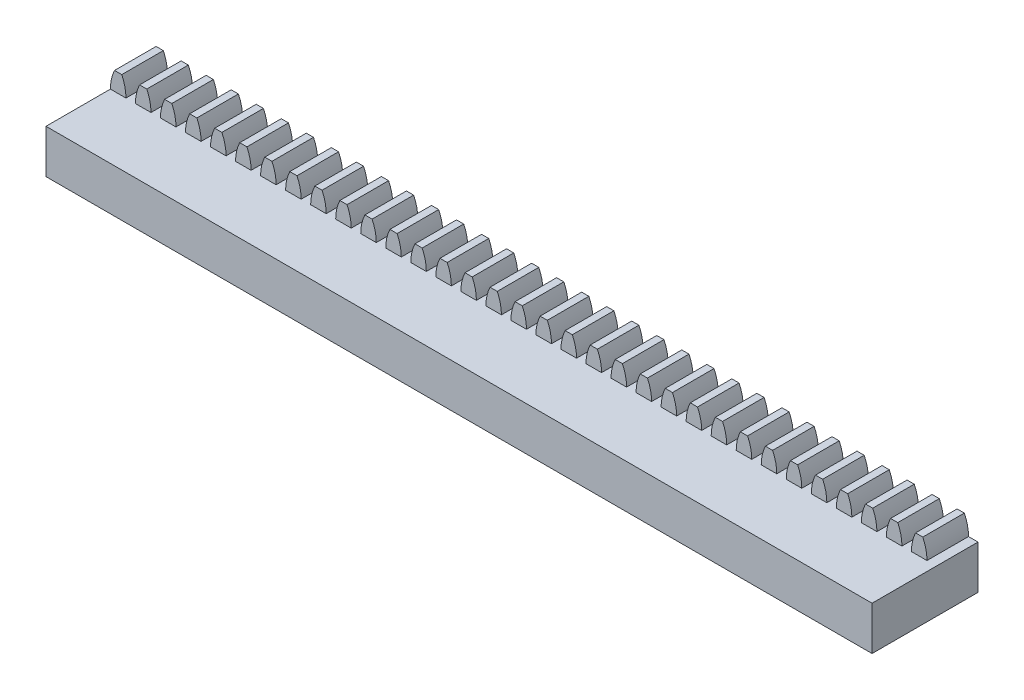
SolidWorks part; units mm, degrees
material "ABS"
ref_plane "Plano frontal" through (0, 0, 0) normal (0, 0, 1) x (1, 0, 0)
ref_plane "Plano superior" through (0, 0, 0) normal (0, 1, 0) x (1, 0, 0)
ref_plane "Plano direito" through (0, 0, 0) normal (1, 0, 0) x (0, 0, -1)
sketch "Esboço1" plane through (0, 0, 0) normal (0, 0, 1) x (1, 0, 0)
  line L0 (-1.7112, 4.5297) -> (-1.0175, 4.5297)
  line L1 (0.6988, 4.5297) -> (1.3925, 4.5297)
  line L2 (0.2978, 2.7713) -> (2.7078, 2.7713)
  line L3 (-2.1122, 2.7713) -> (0.2978, 2.7713)
  line L4 (3.1088, 4.5297) -> (3.8025, 4.5297)
  line L5 (2.7078, 2.7713) -> (5.1178, 2.7713)
  line L6 (5.5188, 4.5297) -> (6.2125, 4.5297)
  line L7 (5.1178, 2.7713) -> (7.5278, 2.7713)
  line L8 (7.9288, 4.5297) -> (8.6225, 4.5297)
  line L9 (7.5278, 2.7713) -> (9.9378, 2.7713)
  line L10 (10.3388, 4.5297) -> (11.0325, 4.5297)
  line L11 (9.9378, 2.7713) -> (12.3478, 2.7713)
  line L12 (12.7488, 4.5297) -> (13.4425, 4.5297)
  line L13 (12.3478, 2.7713) -> (14.7578, 2.7713)
  line L14 (15.1588, 4.5297) -> (15.8525, 4.5297)
  line L15 (14.7578, 2.7713) -> (17.1678, 2.7713)
  line L16 (17.5688, 4.5297) -> (18.2625, 4.5297)
  line L17 (17.1678, 2.7713) -> (19.5778, 2.7713)
  line L18 (19.9788, 4.5297) -> (20.6725, 4.5297)
  line L19 (19.5778, 2.7713) -> (21.9878, 2.7713)
  line L20 (22.3888, 4.5297) -> (23.0825, 4.5297)
  line L21 (21.9878, 2.7713) -> (24.3978, 2.7713)
  line L22 (24.7988, 4.5297) -> (25.4925, 4.5297)
  line L23 (24.3978, 2.7713) -> (26.8078, 2.7713)
  line L24 (27.2088, 4.5297) -> (27.9025, 4.5297)
  line L25 (26.8078, 2.7713) -> (29.2178, 2.7713)
  line L26 (29.6188, 4.5297) -> (30.3125, 4.5297)
  line L27 (29.2178, 2.7713) -> (31.6278, 2.7713)
  line L28 (32.0288, 4.5297) -> (32.7225, 4.5297)
  line L29 (31.6278, 2.7713) -> (34.0378, 2.7713)
  line L30 (34.4388, 4.5297) -> (35.1325, 4.5297)
  line L31 (34.0378, 2.7713) -> (36.4478, 2.7713)
  line L32 (36.8488, 4.5297) -> (37.5425, 4.5297)
  line L33 (36.4478, 2.7713) -> (38.8578, 2.7713)
  line L34 (39.2588, 4.5297) -> (39.9525, 4.5297)
  line L35 (38.8578, 2.7713) -> (41.2678, 2.7713)
  line L36 (41.6688, 4.5297) -> (42.3625, 4.5297)
  line L37 (41.2678, 2.7713) -> (43.6778, 2.7713)
  line L38 (44.0788, 4.5297) -> (44.7725, 4.5297)
  line L39 (43.6778, 2.7713) -> (46.0878, 2.7713)
  line L40 (46.4888, 4.5297) -> (47.1825, 4.5297)
  line L41 (46.0878, 2.7713) -> (48.4978, 2.7713)
  line L42 (77.4178, 2.7713) -> (77.4178, -1.4287)
  line L43 (48.8988, 4.5297) -> (49.5925, 4.5297)
  line L44 (48.4978, 2.7713) -> (50.9078, 2.7713)
  line L45 (51.3088, 4.5297) -> (52.0025, 4.5297)
  line L46 (50.9078, 2.7713) -> (53.3178, 2.7713)
  line L47 (53.7188, 4.5297) -> (54.4125, 4.5297)
  line L48 (53.3178, 2.7713) -> (55.7278, 2.7713)
  line L49 (56.1288, 4.5297) -> (56.8225, 4.5297)
  line L50 (55.7278, 2.7713) -> (58.1378, 2.7713)
  line L51 (58.5388, 4.5297) -> (59.2325, 4.5297)
  line L52 (58.1378, 2.7713) -> (60.5478, 2.7713)
  line L53 (60.9488, 4.5297) -> (61.6425, 4.5297)
  line L54 (60.5478, 2.7713) -> (62.9578, 2.7713)
  line L55 (63.3588, 4.5297) -> (64.0525, 4.5297)
  line L56 (62.9578, 2.7713) -> (65.3678, 2.7713)
  line L57 (65.7688, 4.5297) -> (66.4625, 4.5297)
  line L58 (65.3678, 2.7713) -> (67.7778, 2.7713)
  line L59 (68.1788, 4.5297) -> (68.8725, 4.5297)
  line L60 (67.7778, 2.7713) -> (70.1878, 2.7713)
  line L61 (70.5888, 4.5297) -> (71.2825, 4.5297)
  line L62 (70.1878, 2.7713) -> (72.5978, 2.7713)
  line L63 (72.9988, 4.5297) -> (73.6925, 4.5297)
  line L64 (72.5978, 2.7713) -> (75.0078, 2.7713)
  line L65 (75.4088, 4.5297) -> (76.1025, 4.5297)
  line L66 (75.0078, 2.7713) -> (77.4178, 2.7713)
  line L67 (77.4178, -1.4287) -> (47.8878, -1.4287)
  line L124 (-2.1122, 2.7713) -> (-2.1122, -1.4287)
  line L127 (-2.1122, -1.4287) -> (47.8878, -1.4287)
  line L128 (46.4888, 4.5297) -> (47.1825, 4.5297) [skipped]
  line L129 (46.0878, 2.7713) -> (47.5834, 2.7713) [skipped]
  line L130 (77.4178, 2.7713) -> (79.8278, 2.7713) [skipped]
  line L131 (77.8188, 4.5297) -> (78.5125, 4.5297) [skipped]
  arc A0 (-1.7112, 4.5297) -> (-2.1122, 2.7713) centre (1.944, 2.7713) ccw
  arc A1 (-1.0175, 4.5297) -> (-0.6166, 2.7713) centre (-4.6728, 2.7713) cw
  arc A2 (0.6988, 4.5297) -> (0.2978, 2.7713) centre (4.354, 2.7713) ccw
  arc A3 (1.3925, 4.5297) -> (1.7934, 2.7713) centre (-2.2628, 2.7713) cw
  arc A4 (3.1088, 4.5297) -> (2.7078, 2.7713) centre (6.764, 2.7713) ccw
  arc A5 (3.8025, 4.5297) -> (4.2034, 2.7713) centre (0.1472, 2.7713) cw
  arc A6 (5.5188, 4.5297) -> (5.1178, 2.7713) centre (9.174, 2.7713) ccw
  arc A7 (6.2125, 4.5297) -> (6.6134, 2.7713) centre (2.5572, 2.7713) cw
  arc A8 (7.9288, 4.5297) -> (7.5278, 2.7713) centre (11.584, 2.7713) ccw
  arc A9 (8.6225, 4.5297) -> (9.0234, 2.7713) centre (4.9672, 2.7713) cw
  arc A10 (10.3388, 4.5297) -> (9.9378, 2.7713) centre (13.994, 2.7713) ccw
  arc A11 (11.0325, 4.5297) -> (11.4334, 2.7713) centre (7.3772, 2.7713) cw
  arc A12 (12.7488, 4.5297) -> (12.3478, 2.7713) centre (16.404, 2.7713) ccw
  arc A13 (13.4425, 4.5297) -> (13.8434, 2.7713) centre (9.7872, 2.7713) cw
  arc A14 (15.1588, 4.5297) -> (14.7578, 2.7713) centre (18.814, 2.7713) ccw
  arc A15 (15.8525, 4.5297) -> (16.2534, 2.7713) centre (12.1972, 2.7713) cw
  arc A16 (17.5688, 4.5297) -> (17.1678, 2.7713) centre (21.224, 2.7713) ccw
  arc A17 (18.2625, 4.5297) -> (18.6634, 2.7713) centre (14.6072, 2.7713) cw
  arc A18 (19.9788, 4.5297) -> (19.5778, 2.7713) centre (23.634, 2.7713) ccw
  arc A19 (20.6725, 4.5297) -> (21.0734, 2.7713) centre (17.0172, 2.7713) cw
  arc A20 (22.3888, 4.5297) -> (21.9878, 2.7713) centre (26.044, 2.7713) ccw
  arc A21 (23.0825, 4.5297) -> (23.4834, 2.7713) centre (19.4272, 2.7713) cw
  arc A22 (24.7988, 4.5297) -> (24.3978, 2.7713) centre (28.454, 2.7713) ccw
  arc A23 (25.4925, 4.5297) -> (25.8934, 2.7713) centre (21.8372, 2.7713) cw
  arc A24 (27.2088, 4.5297) -> (26.8078, 2.7713) centre (30.864, 2.7713) ccw
  arc A25 (27.9025, 4.5297) -> (28.3034, 2.7713) centre (24.2472, 2.7713) cw
  arc A26 (29.6188, 4.5297) -> (29.2178, 2.7713) centre (33.274, 2.7713) ccw
  arc A27 (30.3125, 4.5297) -> (30.7134, 2.7713) centre (26.6572, 2.7713) cw
  arc A28 (32.0288, 4.5297) -> (31.6278, 2.7713) centre (35.684, 2.7713) ccw
  arc A29 (32.7225, 4.5297) -> (33.1234, 2.7713) centre (29.0672, 2.7713) cw
  arc A30 (34.4388, 4.5297) -> (34.0378, 2.7713) centre (38.094, 2.7713) ccw
  arc A31 (35.1325, 4.5297) -> (35.5334, 2.7713) centre (31.4772, 2.7713) cw
  arc A32 (36.8488, 4.5297) -> (36.4478, 2.7713) centre (40.504, 2.7713) ccw
  arc A33 (37.5425, 4.5297) -> (37.9434, 2.7713) centre (33.8872, 2.7713) cw
  arc A34 (39.2588, 4.5297) -> (38.8578, 2.7713) centre (42.914, 2.7713) ccw
  arc A35 (39.9525, 4.5297) -> (40.3534, 2.7713) centre (36.2972, 2.7713) cw
  arc A36 (41.6688, 4.5297) -> (41.2678, 2.7713) centre (45.324, 2.7713) ccw
  arc A37 (42.3625, 4.5297) -> (42.7634, 2.7713) centre (38.7072, 2.7713) cw
  arc A38 (44.0788, 4.5297) -> (43.6778, 2.7713) centre (47.734, 2.7713) ccw
  arc A39 (44.7725, 4.5297) -> (45.1734, 2.7713) centre (41.1172, 2.7713) cw
  arc A40 (46.4888, 4.5297) -> (46.0878, 2.7713) centre (50.144, 2.7713) ccw
  arc A41 (47.1825, 4.5297) -> (47.5834, 2.7713) centre (43.5272, 2.7713) cw
  arc A42 (47.1825, 4.5297) -> (47.5834, 2.7713) centre (43.5272, 2.7713) cw [skipped]
  arc A43 (46.4888, 4.5297) -> (46.0878, 2.7713) centre (50.144, 2.7713) ccw [skipped]
  arc A44 (48.8988, 4.5297) -> (48.4978, 2.7713) centre (52.554, 2.7713) ccw
  arc A45 (49.5925, 4.5297) -> (49.9934, 2.7713) centre (45.9372, 2.7713) cw
  arc A46 (51.3088, 4.5297) -> (50.9078, 2.7713) centre (54.964, 2.7713) ccw
  arc A47 (52.0025, 4.5297) -> (52.4034, 2.7713) centre (48.3472, 2.7713) cw
  arc A48 (53.7188, 4.5297) -> (53.3178, 2.7713) centre (57.374, 2.7713) ccw
  arc A49 (54.4125, 4.5297) -> (54.8134, 2.7713) centre (50.7572, 2.7713) cw
  arc A50 (56.1288, 4.5297) -> (55.7278, 2.7713) centre (59.784, 2.7713) ccw
  arc A51 (56.8225, 4.5297) -> (57.2234, 2.7713) centre (53.1672, 2.7713) cw
  arc A52 (58.5388, 4.5297) -> (58.1378, 2.7713) centre (62.194, 2.7713) ccw
  arc A53 (59.2325, 4.5297) -> (59.6334, 2.7713) centre (55.5772, 2.7713) cw
  arc A54 (60.9488, 4.5297) -> (60.5478, 2.7713) centre (64.604, 2.7713) ccw
  arc A55 (61.6425, 4.5297) -> (62.0434, 2.7713) centre (57.9872, 2.7713) cw
  arc A56 (63.3588, 4.5297) -> (62.9578, 2.7713) centre (67.014, 2.7713) ccw
  arc A57 (64.0525, 4.5297) -> (64.4534, 2.7713) centre (60.3972, 2.7713) cw
  arc A58 (65.7688, 4.5297) -> (65.3678, 2.7713) centre (69.424, 2.7713) ccw
  arc A59 (66.4625, 4.5297) -> (66.8634, 2.7713) centre (62.8072, 2.7713) cw
  arc A60 (68.1788, 4.5297) -> (67.7778, 2.7713) centre (71.834, 2.7713) ccw
  arc A61 (68.8725, 4.5297) -> (69.2734, 2.7713) centre (65.2172, 2.7713) cw
  arc A62 (70.5888, 4.5297) -> (70.1878, 2.7713) centre (74.244, 2.7713) ccw
  arc A63 (71.2825, 4.5297) -> (71.6834, 2.7713) centre (67.6272, 2.7713) cw
  arc A64 (72.9988, 4.5297) -> (72.5978, 2.7713) centre (76.654, 2.7713) ccw
  arc A65 (73.6925, 4.5297) -> (74.0934, 2.7713) centre (70.0372, 2.7713) cw
  arc A66 (75.4088, 4.5297) -> (75.0078, 2.7713) centre (79.064, 2.7713) ccw
  arc A67 (76.1025, 4.5297) -> (76.5034, 2.7713) centre (72.4472, 2.7713) cw
  arc A70 (78.5125, 4.5297) -> (78.9134, 2.7713) centre (74.8572, 2.7713) cw [skipped]
  arc A71 (77.8188, 4.5297) -> (77.4178, 2.7713) centre (81.474, 2.7713) ccw [skipped]
  dimension "D1" = 0.9144
  dimension "D3" = 21
  dimension "D4" = 0.6937
  dimension "D5" = 1.4956
  dimension "D7" = 79.53
  dimension "D10" = 4.2
  dimension "D6" = 15
extrude "Ressalto-extrusão1" add sketch "Esboço1" along normal mid plane 4 contours A1 L0 A0 L3 | A3 L1 A2 L2 | A5 L4 A4 L5 | A7 L6 A6 L7 | A9 L8 A8 L9 | A11 L10 A10 L11 | A13 L12 A12 L13 | A15 L14 A14 L15 | A17 L16 A16 L17 | A19 L18 A18 L19 | A21 L20 A20 L21 | A23 L22 A22 L23 | A25 L24 A24 L25 | A27 L26 A26 L27 | A29 L28 A28 L29 | A31 L30 A30 L31 | A33 L32 A32 L33 | A35 L34 A34 L35 | A37 L36 A36 L37 | A39 L38 A38 L39 | L40 A40 | A45 L43 A44 L44 | A47 L45 A46 L46 | A49 L47 A48 L48 | A51 L49 A50 L50 | A53 L51 A52 L52 | A55 L53 A54 L54 | A57 L55 A56 L56 | A59 L57 A58 L58 | A61 L59 A60 L60 | A63 L61 A62 L62 | A65 L63 A64 L64 | A67 L65 A66 L66 region at (-1.3644, 3.5563, 0) region at (1.0456, 3.5563, 0) region at (3.4556, 3.5563, 0) region at (75.7556, 3.5563, 0) region at (5.8656, 3.5563, 0) region at (73.3456, 3.5563, 0) region at (8.2756, 3.5563, 0) region at (70.9356, 3.5563, 0) region at (10.6856, 3.5563, 0) region at (68.5256, 3.5563, 0) region at (13.0956, 3.5563, 0) region at (66.1156, 3.5563, 0) region at (15.5056, 3.5563, 0) region at (63.7056, 3.5563, 0) region at (17.9156, 3.5563, 0) region at (61.2956, 3.5563, 0) region at (20.3256, 3.5563, 0) region at (58.8856, 3.5563, 0) region at (22.7356, 3.5563, 0) region at (56.4756, 3.5563, 0) region at (25.1456, 3.5563, 0) region at (54.0656, 3.5563, 0) region at (27.5556, 3.5563, 0) region at (51.6556, 3.5563, 0) region at (29.9656, 3.5563, 0) region at (49.2456, 3.5563, 0) region at (32.3756, 3.5563, 0) region at (46.8356, 3.5563, 0) region at (34.7856, 3.5563, 0) region at (44.4256, 3.5563, 0) region at (37.1956, 3.5563, 0) region at (42.0156, 3.5563, 0) region at (39.6056, 3.5563, 0)
extrude "Ressalto-extrusão2" add sketch "Esboço1<7>" along normal blind 8.2 and the other way blind 2 contours L124 L127 L39 L37 L35 L33 L31 L29 L27 L25 L23 L21 L19 L17 L15 L13 L11 L9 L7 L5 L2 L3 region at (37.6528, 0.6713, 0)
sketch "Esboço1<7>" plane through (0, 0, 0) normal (0, 0, 1) x (1, 0, 0) same geometry as "Esboço1"
